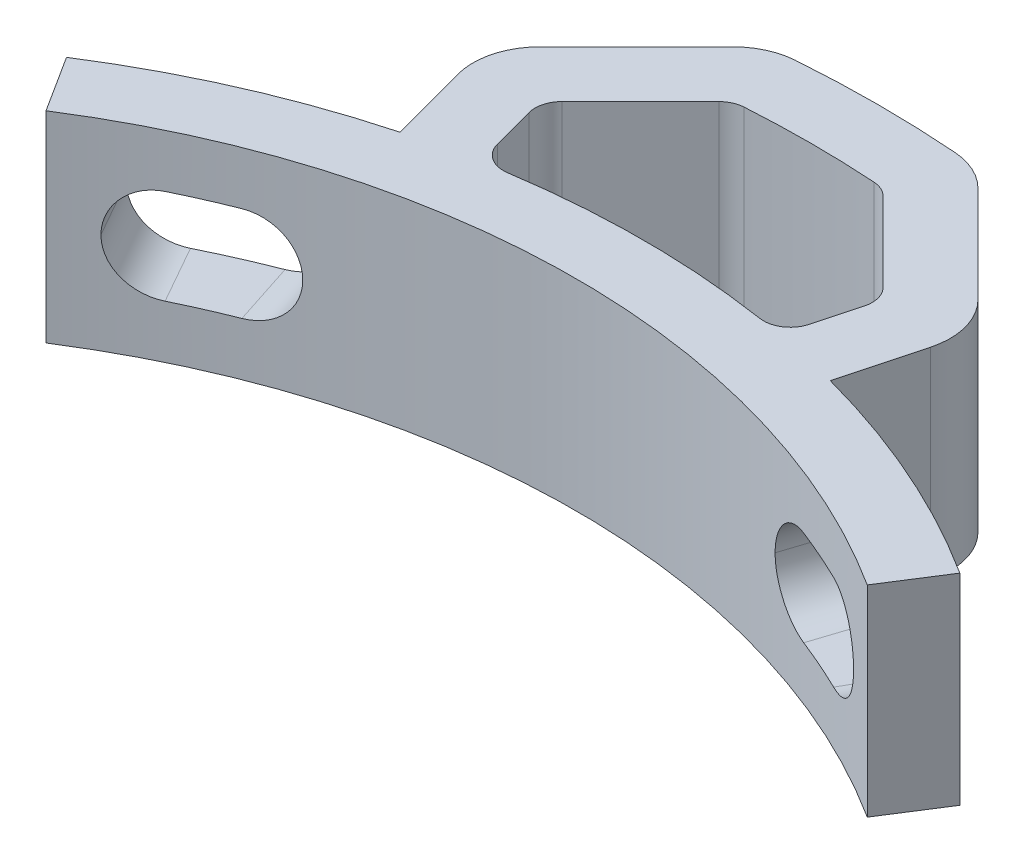
SolidWorks part; units mm, degrees
ref_plane "Front Plane" through (0, 0, 0) normal (0, 0, 1) x (1, 0, 0)
ref_plane "Top Plane" through (0, 0, 0) normal (0, 1, 0) x (1, 0, 0)
ref_plane "Right Plane" through (0, 0, 0) normal (1, 0, 0) x (0, 0, -1)
sketch "Sketch1" plane through (0, 0, 0) normal (0, 1, 0) x (1, 0, 0)
  line L27 (-19.4476, 30.5266) -> (0, 0) construction
  line L28 (0, 0) -> (19.4476, 30.5266) construction
  line L29 (0, 0) -> (0, 36.195) construction
  line L30 (-10.1897, 38.0285) -> (0, 0) construction
  line L33 (0, 0) -> (10.1897, 38.0285) construction
  line L34 (-19.4476, 30.5266) -> (-21.1535, 33.2043)
  line L35 (19.4476, 30.5266) -> (21.1535, 33.2043)
  line L36 (-13.0658, 48.7624) -> (-10.1897, 38.0285)
  line L37 (13.0658, 48.7624) -> (10.1897, 38.0285)
  arc A2 (19.4476, 30.5266) -> (-19.4476, 30.5266) centre (0, 0) ccw
  arc A3 (13.0658, 48.7624) -> (-13.0658, 48.7624) centre (0, 0) ccw
  arc A4 (21.1535, 33.2043) -> (10.1897, 38.0285) centre (0, 0) ccw
  arc A5 (-10.1897, 38.0285) -> (-21.1535, 33.2043) centre (0, 0) ccw
  dimension "D3" = 36.195
  dimension "D1" = 32.5
  dimension "D2" = 32.5
  dimension "D4" = 14.2875
  dimension "D5" = 15
  dimension "D6" = 15
  dimension "D7" = 3.175
extrude "Boss-Extrude1" add sketch "Sketch1" along normal mid plane 9.525
chamfer "Chamfer1" distance 5.3975 angle 60 2 edges at (-13.0658, 0, -48.7624) (13.0658, 0, -48.7624) first distance on face at (-11.6278, 0, -43.3954) first distance on face at (11.6278, 0, -43.3954)
sketch "Sketch2" plane through (0, 0, 0) normal (0, 1, 0) x (1, 0, 0)
  line L0 (-12.166, 37.4431) -> (-11.1849, 34.4235)
  line L1 (-17.8233, 31.5025) -> (-19.3867, 34.2659)
  line L2 (-11.1849, 34.4235) -> (0, 0) construction
  line L3 (0, 0) -> (-17.8233, 31.5025) construction
  line L4 (-21.1535, 33.2043) -> (-19.4476, 30.5266) construction
  line L5 (-11.6689, 43.5488) -> (-10.1897, 38.0285) construction
  arc A1 (19.4476, 30.5266) -> (-19.4476, 30.5266) centre (0, 0) ccw construction
  arc A2 (-10.1897, 38.0285) -> (-21.1535, 33.2043) centre (0, 0) ccw construction
  arc A4 (-11.1849, 34.4235) -> (-17.8233, 31.5025) centre (0, 0) ccw
  arc A5 (-12.166, 37.4431) -> (-19.3867, 34.2659) centre (0, 0) ccw
  dimension "D1" = 3
  dimension "D2" = 3
extrude "Cut-Extrude1" cut sketch "Sketch2" against normal mid plane 4.5
fillet "Fillet1" radius 2.25 4 edges at (-18.605, -2.25, -32.8842) (-18.605, 2.25, -32.8842) (-11.6754, 2.25, -35.9333) (-11.6754, -2.25, -35.9333)
mirror "Mirror1" about plane through (0, 0, 0) normal (1, 0, 0) of "Fillet1", "Cut-Extrude1"
fillet "Fillet2" radius 3.175 4 edges at (11.6689, 0, -43.5488) (4.9815, 0, -50.2361) (-4.9815, 0, -50.2361) (-11.6689, 0, -43.5488)
sketch "Sketch3" plane through (0, 4.7625, 0) normal (0, 1, 0) x (1, 0, 0)
  line L8 (7.1229, 38.8503) -> (8.1276, 42.5999)
  line L9 (8.1276, 42.5999) -> (3.5537, 47.1738)
  line L10 (-8.1276, 42.5999) -> (-7.1229, 38.8503)
  line L11 (-3.5537, 47.1738) -> (-8.1276, 42.5999)
  line L12 (7.0897, 38.7264) -> (8.1276, 42.5999)
  line L13 (8.1276, 42.5999) -> (3.5537, 47.1738)
  line L14 (-8.1276, 42.5999) -> (-7.0897, 38.7264)
  line L15 (-3.5537, 47.1738) -> (-8.1276, 42.5999)
  arc A5 (-10.1897, 38.0285) -> (-21.1535, 33.2043) centre (0, 0) ccw construction
  arc A6 (7.0897, 38.7264) -> (-7.0897, 38.7264) centre (0, 0) ccw
  arc A10 (3.5537, 47.1738) -> (-3.5537, 47.1738) centre (0, 0) ccw
  arc A11 (3.5537, 47.1738) -> (-3.5537, 47.1738) centre (0, 0) ccw
  point P0 (5.2134, 38.1883)
  dimension "D1" = 3.175
extrude "Cut-Extrude2" cut sketch "Sketch3" against normal through all
fillet "Fillet3" radius 1.27 6 edges at (-7.0897, 0, -38.7264) (7.0897, 0, -38.7264) (8.1276, 0, -42.5999) (3.5537, 0, -47.1738) (-3.5537, 0, -47.1738) (-8.1276, 0, -42.5999)
equation "\"D2@Sketch1\"=\"D1@Sketch1\""
equation "\"D6@Sketch1\"=\"D5@Sketch1\""
equation "\"D2@Sketch2\"=\"D1@Sketch2\""
